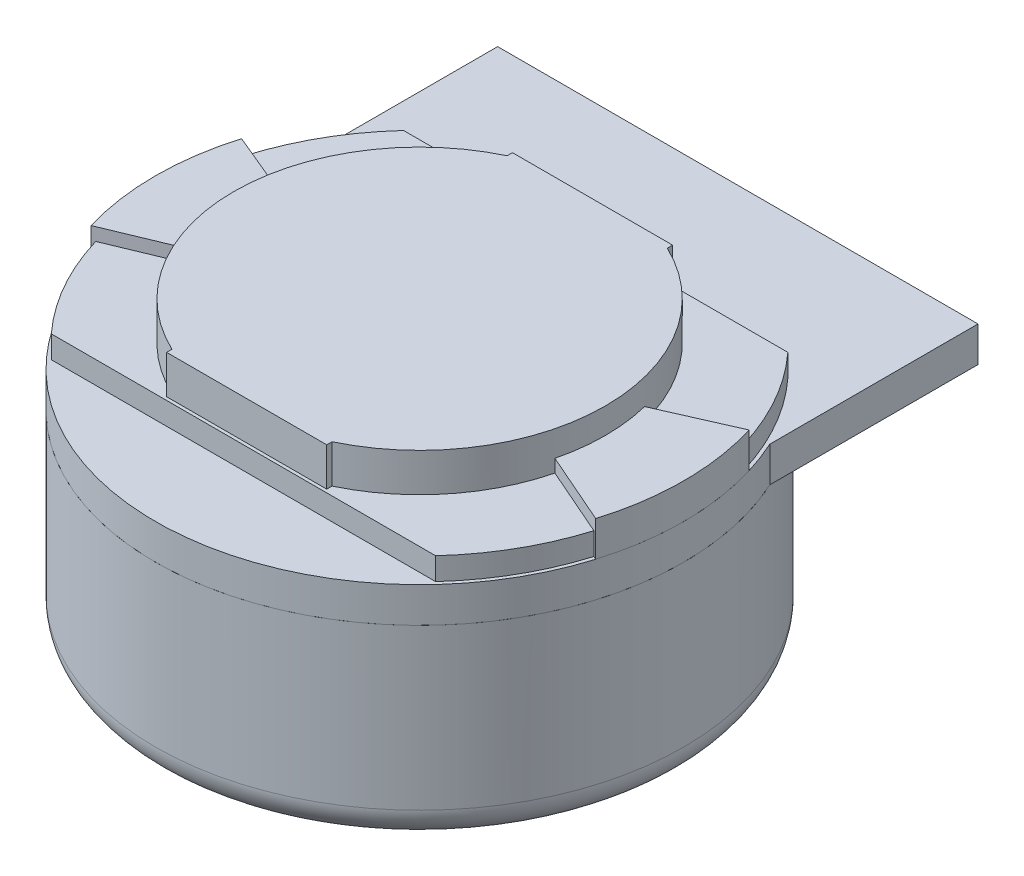
SolidWorks part; units mm, degrees
ref_plane "Front Plane" through (0, 0, 0) normal (0, 0, 1) x (1, 0, 0)
ref_plane "Top Plane" through (0, 0, 0) normal (0, 1, 0) x (1, 0, 0)
ref_plane "Right Plane" through (0, 0, 0) normal (1, 0, 0) x (0, 0, -1)
sketch "Sketch1" plane through (0, 0, 0) normal (0, 1, 0) x (1, 0, 0)
  circle A0 centre (0, 0) radius 8.25
  dimension "D1" = 16.5
extrude "Boss-Extrude1" add sketch "Sketch1" along normal blind 6
fillet "Fillet1" radius 1 1 edges at (0, 0, 8.25)
sketch "Sketch2" plane through (0, 6, 0) normal (0, 1, 0) x (1, 0, 0)
  line L0 (-6, 5.6624) -> (6, 5.6624)
  circle A0 centre (0, 0) radius 8.25 construction
  arc A1 (6, 5.6624) -> (-6, 5.6624) centre (0, 0) ccw
  point P5 (8.0905, 1.6143)
  point P6 (-7.3597, 3.7279)
  point P7 (8.0905, 1.6143)
  point P9 (7.0067, 4.3553)
  point P10 (0, 0)
  point P11 (0, 0)
  point P12 (6.9933, 4.3553)
  point P13 (6.8186, 4.6443)
  point P14 (7.0027, 4.3705)
  point P15 (7.4979, 3.4414)
  point P16 (-7.0027, 4.3703)
  point P17 (5.9967, 5.6659)
  dimension "D1" = 12
  dimension "D2" = 5.6624
extrude "Cut-Extrude1" cut sketch "Sketch2" against normal blind 2
sketch "Sketch3" plane through (0, 6, 0) normal (0, 1, 0) x (1, 0, 0)
  circle A0 centre (0, 0) radius 8
  dimension "D1" = 16
extrude "Cut-Extrude2" cut sketch "Sketch3" against normal blind 5.6
sketch "Sketch4" plane through (0, 6, 0) normal (0, 1, 0) x (1, 0, 0)
  line L6 (-7.5, 3.4369) -> (-7.5, 9.9369)
  line L7 (-7.5, 9.9369) -> (7.5, 9.9369)
  line L8 (7.5, 3.4369) -> (7.5, 9.9369)
  arc A1 (-6, 5.6624) -> (6, 5.6624) centre (0, 0) ccw construction
  arc A2 (-7.5, 3.4369) -> (7.5, 3.4369) centre (0, 0) ccw
  dimension "D1" = 15
  dimension "D2" = 7.5
  dimension "D3" = 6.5
extrude "Boss-Extrude2" add sketch "Sketch4" along normal blind 1.1 separate body
sketch "Sketch6" plane through (0, 7.1, 0) normal (0, 1, 0) x (1, 0, 0)
  line L1 (-6, 5.5) -> (6, 5.5)
  line L3 (-6, -5.5) -> (6, -5.5)
  arc A0 (-6, 5.5) -> (-6, -5.5) centre (0, 0) ccw
  arc A1 (6, -5.5) -> (6, 5.5) centre (0, 0) ccw
  dimension "D1" = 11
  dimension "D2" = 5.5
  dimension "D3" = 12
  dimension "D4" = 11
extrude "Boss-Extrude3" add sketch "Sketch6" along normal blind 0.7 separate body
sketch "Sketch7" plane through (0, 7.8, 0) normal (0, 1, 0) x (1, 0, 0)
  line L0 (2.5, -5.4) -> (2.5, -5.2335)
  line L1 (-2.5, -5.4) -> (2.5, -5.4)
  line L3 (-2.5, 5.4) -> (2.5, 5.4)
  line L5 (-2.5, -5.4) -> (-2.5, -5.2335)
  line L6 (-2.5, 5.2335) -> (-2.5, 5.4)
  line L7 (2.5, 5.2335) -> (2.5, 5.4)
  arc A0 (-2.5, -5.2335) -> (-2.5, 5.2335) centre (0, 0) cw
  arc A1 (2.5, 5.2335) -> (2.5, -5.2335) centre (0, 0) cw
  dimension "D5" = 5.8
  dimension "D6" = 5.8
  dimension "D1" = 5
  dimension "D2" = 5.4
  dimension "D3" = 10.8
  dimension "D4" = 5.4
  dimension "D7" = 0.1665
  dimension "D8" = 0.1665
extrude "Boss-Extrude4" add sketch "Sketch7" along normal blind 1.2
sketch "Sketch11" plane through (0, 7.1, 0) normal (0, 1, 0) x (1, 0, 0)
  line L2 (-7.9082, 2.35) -> (-5.6294, 1.3965)
  line L3 (-7.9082, -2.35) -> (-5.6276, -1.4035)
  line L4 (7.7928, 2.35) -> (5.6294, 1.3965)
  line L6 (5.6278, -1.4028) -> (7.7928, -2.35)
  arc A0 (-7.5, 3.4369) -> (7.5, 3.4369) centre (0, 0) ccw construction
  arc A1 (-2.5, 5.2335) -> (-2.5, -5.2335) centre (0, 0) ccw construction
  arc A2 (-7.9082, 2.35) -> (-7.9082, -2.35) centre (0, 0) ccw
  arc A3 (-5.6294, 1.3965) -> (-5.6276, -1.4035) centre (0, 0) ccw
  arc A4 (6, -5.5) -> (6, 5.5) centre (0, 0) ccw construction
  arc A5 (2.5, -5.2335) -> (2.5, 5.2335) centre (0, 0) ccw construction
  arc A6 (7.7928, 2.35) -> (7.7928, -2.35) centre (0, 0) cw
  arc A7 (5.6278, -1.4028) -> (5.6294, 1.3965) centre (0, 0) ccw
  point P24 (0, 0)
  dimension "D1" = 4.7
  dimension "D3" = 2.8
extrude "Cut-Extrude4" cut sketch "Sketch11" along normal blind 0.7
sketch "Sketch12" plane through (0, 7.1, 0) normal (0, 1, 0) x (1, 0, 0)
  line L0 (-5.6276, -1.4035) -> (-7.9082, -2.3502)
  line L2 (-7.9082, 2.3502) -> (-5.6294, 1.3965)
  line L4 (5.6294, 1.3965) -> (7.8947, 2.3949)
  line L5 (5.6278, -1.4028) -> (7.8947, -2.3949)
  arc A0 (-2.5, 5.2335) -> (-2.5, -5.2335) centre (0, 0) ccw construction
  arc A1 (-5.6276, -1.4035) -> (-2.5, -5.2335) centre (0, 0) ccw construction
  arc A2 (-7.5, 3.4369) -> (7.5, 3.4369) centre (0, 0) ccw construction
  arc A3 (-5.6294, 1.3965) -> (-5.6276, -1.4035) centre (0, 0) ccw
  arc A4 (-7.9082, 2.3502) -> (-7.9082, -2.3502) centre (0, 0) ccw
  arc A5 (5.6294, 1.3965) -> (5.6278, -1.4028) centre (0, 0) cw
  arc A6 (7.8947, -2.3949) -> (7.8947, 2.3949) centre (0, 0) ccw
  point P24 (0, 0)
  point P25 (7.8947, 2.395)
extrude "Boss-Extrude6" add sketch "Sketch12" along normal blind 1.1 separate body
